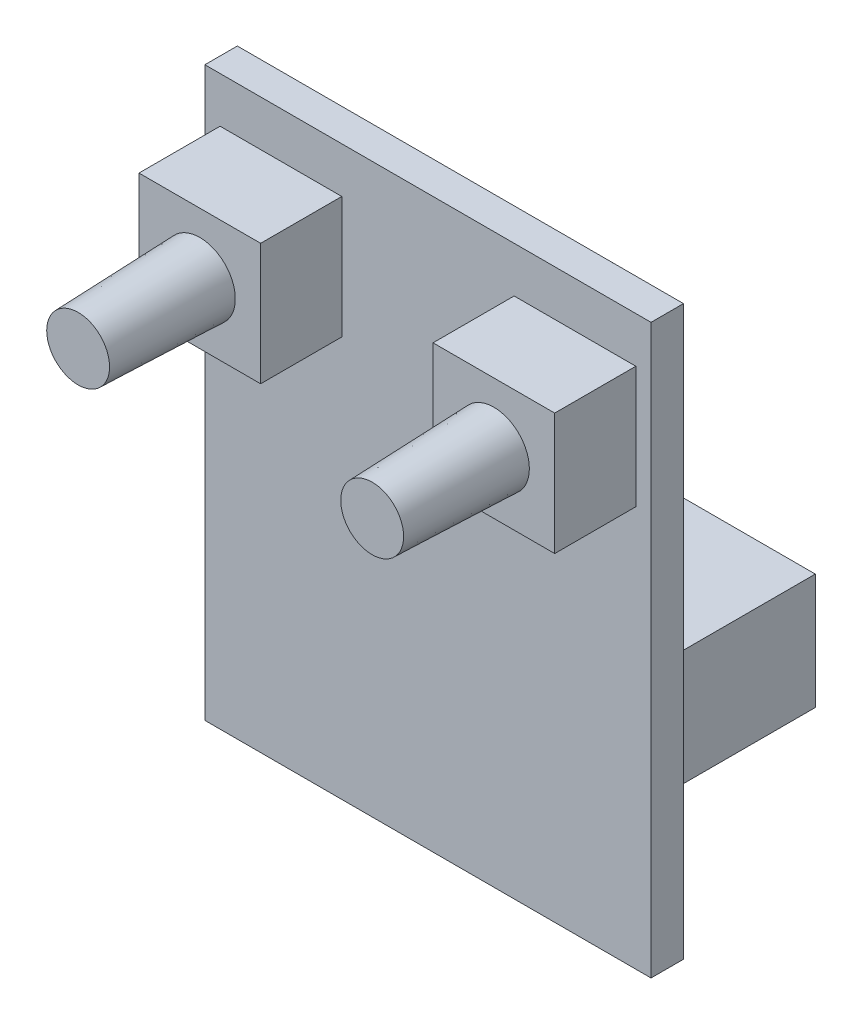
SolidWorks part; units mm, degrees
ref_plane "Front plane" through (0, 0, 0) normal (0, 0, 1) x (1, 0, 0)
ref_plane "Top plane" through (0, 0, 0) normal (0, 1, 0) x (1, 0, 0)
ref_plane "Right Plane" through (0, 0, 0) normal (1, 0, 0) x (0, 0, -1)
sketch "Sketch1" plane through (0, 0, 0) normal (0, 0, 1) x (1, 0, 0)
  line L1 (-11, 0) -> (11, 0)
  line L2 (-11, 0) -> (-11, 28)
  line L3 (-11, 28) -> (11, 28)
  line L4 (11, 0) -> (11, 28)
  dimension "D1" = 22
  dimension "D2" = 28
extrude "Boss-Extrude1" add sketch "Sketch1" along normal blind 1.6
sketch "Sketch2" plane through (0, 0, 1.6) normal (0, 0, 1) x (1, 0, 0)
  line L0 (-11, 0) -> (11, 0) construction
  line L5 (4.25, 25.75) -> (10.25, 25.75)
  line L6 (4.25, 25.75) -> (4.25, 19.75)
  line L7 (4.25, 19.75) -> (10.25, 19.75)
  line L8 (10.25, 25.75) -> (10.25, 19.75)
  point P0 (10.25, 22.75)
  point P3 (7.25, 19.75)
  dimension "D1" = 22.75
  dimension "D2" = 6
  dimension "D3" = 7.25
extrude "Boss-Extrude2" add sketch "Sketch2" along normal blind 4
sketch "Sketch3" plane through (0, 0, 0) normal (0, 0, -1) x (-1, 0, 0)
  line L1 (-10.5, 7) -> (2, 7)
  line L2 (-10.5, 7) -> (-10.5, 12.7)
  line L3 (-10.5, 12.7) -> (2, 12.7)
  line L4 (2, 7) -> (2, 12.7)
  line L6 (-10.5, 7) -> (10.5, 7) construction
  line L7 (3, 7) -> (10.5, 7)
  line L8 (3, 7) -> (3, 12.7)
  line L9 (3, 12.7) -> (10.5, 12.7)
  line L10 (10.5, 7) -> (10.5, 12.7)
  line L11 (11, 0) -> (-11, 0) construction
  point P13 (0, 7)
  point P16 (0, 0)
  dimension "D1" = 12.5
  dimension "D2" = 5.7
  dimension "D3" = 7
  dimension "D4" = 7.5
  dimension "D5" = 1
extrude "Boss-Extrude3" add sketch "Sketch3" along normal blind 7
ref_plane "Plane1" through (0, 0, 11.6) normal (0, 0, 1) x (1, 0, 0)
sketch "Sketch5" plane through (0, 0, 11.6) normal (0, 0, 1) x (1, 0, 0)
  line L0 (4.25, 19.75) -> (10.25, 25.75) construction
  circle A0 centre (7.25, 22.75) radius 1.55
  dimension "D1" = 3.1
sketch "Sketch6" plane through (0, 0, 5.6) normal (0, 0, 1) x (1, 0, 0)
  circle A0 centre (7.25, 22.75) radius 1.75
  dimension "D1" = 3.5
loft "Loft1" add profiles "Sketch5", "Sketch6" connector at (8.7705, 23.051, 11.6) connector at (8.9714, 23.0649, 5.6)
mirror "Mirror1" about plane through (0, 0, 0) normal (1, 0, 0) of "Loft1", "Boss-Extrude2"
